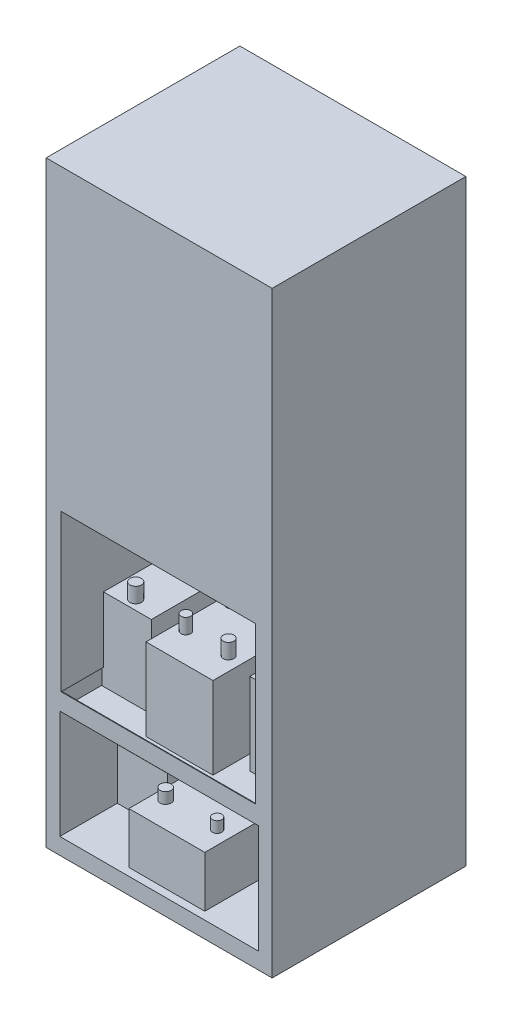
SolidWorks part; units mm, degrees
ref_plane "Alzado" through (0, 0, 0) normal (0, 0, 1) x (1, 0, 0)
ref_plane "Planta" through (0, 0, 0) normal (0, 1, 0) x (1, 0, 0)
ref_plane "Vista lateral" through (0, 0, 0) normal (1, 0, 0) x (0, 0, -1)
sketch "Croquis1" plane through (0, 0, 0) normal (0, 1, 0) x (1, 0, 0)
  line L1 (-350, 300) -> (350, 300)
  line L2 (-350, 300) -> (-350, -300)
  line L3 (-350, -300) -> (350, -300)
  line L4 (350, 300) -> (350, -300)
  line L5 (-350, 300) -> (350, -300) construction
  line L6 (-350, -300) -> (350, 300) construction
  point P0 (0, 0)
  dimension "D1" = 700
  dimension "D2" = 600
extrude "Saliente-Extruir1" add sketch "Croquis1" along normal blind 1850
sketch "Croquis2" plane through (0, 0, 300) normal (0, 0, 1) x (1, 0, 0)
  line L1 (-307.6068, 50.9) -> (307.6068, 50.9)
  line L2 (-307.6068, 50.9) -> (-307.6068, 387.2896)
  line L3 (-307.6068, 387.2896) -> (307.6068, 387.2896)
  line L4 (307.6068, 50.9) -> (307.6068, 387.2896)
  line L5 (-307.6068, 50.9) -> (307.6068, 387.2896) construction
  line L6 (-307.6068, 387.2896) -> (307.6068, 50.9) construction
  point P0 (0, 219.0948)
  point P5 (0, 219.0948)
extrude "Cortar-Extruir1" cut sketch "Croquis2" against normal blind 1850
sketch "Croquis3" plane through (0, 0, 300) normal (0, 0, 1) x (1, 0, 0)
  line L1 (-303.7405, 925) -> (297.7312, 925)
  line L2 (-303.7405, 925) -> (-303.7405, 440.9417)
  line L3 (-303.7405, 440.9417) -> (297.7312, 440.9417)
  line L4 (297.7312, 925) -> (297.7312, 440.9417)
  line L5 (-303.7405, 925) -> (297.7312, 440.9417) construction
  line L6 (-303.7405, 440.9417) -> (297.7312, 925) construction
  point P0 (-3.0046, 682.9709)
  point P5 (297.7312, 929.4263)
  point P6 (-303.7405, 925)
extrude "Cortar-Extruir2" cut sketch "Croquis3" against normal blind 1850
shell "Vaciado1" thickness 2 removed face at (-3.0046, 440.9417, 0)
sketch "Croquis4" plane through (0, 389.2896, 0) normal (0, 1, 0) x (1, 0, 0)
  line L1 (149.6111, 168.6997) -> (305.4222, 168.6997)
  line L2 (149.6111, 168.6997) -> (149.6111, -168.6997)
  line L3 (149.6111, -168.6997) -> (305.4222, -168.6997)
  line L4 (305.4222, 168.6997) -> (305.4222, -168.6997)
  line L5 (149.6111, 168.6997) -> (305.4222, -168.6997) construction
  line L6 (149.6111, -168.6997) -> (305.4222, 168.6997) construction
  line L7 (-103.6465, 236.9965) -> (103.6465, 236.9965)
  line L8 (-103.6465, 236.9965) -> (-103.6465, -236.9965)
  line L9 (-103.6465, -236.9965) -> (103.6465, -236.9965)
  line L10 (103.6465, 236.9965) -> (103.6465, -236.9965)
  line L11 (-103.6465, 236.9965) -> (103.6465, -236.9965) construction
  line L12 (-103.6465, -236.9965) -> (103.6465, 236.9965) construction
  line L13 (-308.6569, 166.2136) -> (-155.4697, 166.2136)
  line L14 (-308.6569, 166.2136) -> (-308.6569, -168.6997)
  line L15 (-308.6569, -168.6997) -> (-155.4697, -168.6997)
  line L16 (-155.4697, 166.2136) -> (-155.4697, -168.6997)
  line L17 (-308.6569, 166.2136) -> (-155.4697, -168.6997) construction
  line L18 (-308.6569, -168.6997) -> (-155.4697, 166.2136) construction
  point P0 (227.5167, 0)
  point P5 (0, 0)
  point P11 (-232.0633, -1.2431)
  point P16 (227.5167, 0)
  point P17 (-206.029, 0)
  point P18 (103.6465, 236.9965)
  point P19 (-236.3645, 0)
  point P20 (-155.4697, 166.2136)
extrude "Saliente-Extruir2" add sketch "Croquis4" along normal blind 254
sketch "Croquis5" plane through (0, 643.2896, 0) normal (0, 1, 0) x (1, 0, 0)
  circle A0 centre (230.0446, -120.7102) radius 17.6957
  circle A1 centre (230.0446, 47.3993) radius 17.6957
  circle A2 centre (-71.1508, -146.027) radius 14.8785
  circle A3 centre (-71.1508, 0) radius 20.0461
  circle A4 centre (-234.15, -138.406) radius 17.6957
  circle A5 centre (-234.15, 47.3993) radius 15.6127
  circle A6 centre (-71.1508, 166.6036) radius 20.0697
  circle A7 centre (61.0037, 0) radius 21.5153
  circle A8 centre (61.0037, 166.6036) radius 19.1168
  circle A9 centre (61.0037, -146.027) radius 16.4298
extrude "Saliente-Extruir3" add sketch "Croquis5" along normal blind 47
sketch "Croquis6" plane through (0, 50.9, 0) normal (0, 1, 0) x (1, 0, 0)
  line L1 (117.5503, -276.1799) -> (-117.5503, -276.1799)
  line L2 (117.5503, -276.1799) -> (117.5503, 276.1799)
  line L3 (117.5503, 276.1799) -> (-117.5503, 276.1799)
  line L4 (-117.5503, -276.1799) -> (-117.5503, 276.1799)
  line L5 (117.5503, -276.1799) -> (-117.5503, 276.1799) construction
  line L6 (117.5503, 276.1799) -> (-117.5503, -276.1799) construction
  line L7 (-152.4825, -121.9742) -> (-307.6068, -121.9742)
  line L8 (-152.4825, -121.9742) -> (-152.4825, 121.9742)
  line L9 (-152.4825, 121.9742) -> (-307.6068, 121.9742)
  line L10 (-307.6068, -121.9742) -> (-307.6068, 121.9742)
  line L11 (-152.4825, -121.9742) -> (-307.6068, 121.9742) construction
  line L12 (-152.4825, 121.9742) -> (-307.6068, -121.9742) construction
  line L13 (289.4517, -121.9742) -> (152.9417, -121.9742)
  line L14 (289.4517, -121.9742) -> (289.4517, 121.9742)
  line L15 (289.4517, 121.9742) -> (152.9417, 121.9742)
  line L16 (152.9417, -121.9742) -> (152.9417, 121.9742)
  line L17 (289.4517, -121.9742) -> (152.9417, 121.9742) construction
  line L18 (289.4517, 121.9742) -> (152.9417, -121.9742) construction
  point P0 (0, 0)
  point P6 (-230.0446, 0)
  point P11 (221.1967, 0)
  point P16 (117.5503, 276.1799)
extrude "Saliente-Extruir4" add sketch "Croquis6" along normal blind 158
sketch "Croquis7" plane through (0, 208.9, 0) normal (0, 1, 0) x (1, 0, 0)
  circle A0 centre (220.4901, -83.4417) radius 21.3099
  circle A1 centre (220.4901, 65.5487) radius 19.7092
  circle A2 centre (-83.7177, -196.0122) radius 17.1385
  circle A3 centre (75.6701, -196.0122) radius 14.5387
  circle A4 centre (-83.7177, 0) radius 19.1962
  circle A5 centre (75.6701, 5.9526) radius 15.4246
  circle A6 centre (-83.7177, 184.741) radius 17.9954
  circle A7 centre (75.6701, 184.741) radius 20.52
  circle A8 centre (-230.0446, -62.1317) radius 17.445
  circle A9 centre (-230.0446, 45.8395) radius 21.1159
extrude "Saliente-Extruir5" add sketch "Croquis7" along normal blind 34
sketch "Croquis8" plane through (0, 0, -300) normal (0, 0, -1) x (-1, 0, 0)
  line L1 (-250.0903, 1244.3934) -> (250.0903, 1244.3934)
  line L2 (-300.0903, 1294.3934) -> (-300.0903, 1716.6284)
  line L3 (-250.0903, 1766.6284) -> (250.0903, 1766.6284)
  line L4 (300.0903, 1294.3934) -> (300.0903, 1716.6284)
  line L5 (-300.0903, 1244.3934) -> (300.0903, 1766.6284) construction
  line L6 (-300.0903, 1766.6284) -> (300.0903, 1244.3934) construction
  arc A0 (-250.0903, 1244.3934) -> (-300.0903, 1294.3934) centre (-250.0903, 1294.3934) cw
  arc A1 (250.0903, 1244.3934) -> (300.0903, 1294.3934) centre (250.0903, 1294.3934) ccw
  arc A2 (250.0903, 1766.6284) -> (300.0903, 1716.6284) centre (250.0903, 1716.6284) cw
  arc A3 (-300.0903, 1716.6284) -> (-250.0903, 1766.6284) centre (-250.0903, 1716.6284) cw
  point P0 (0, 1505.5109)
  point P5 (0, 1570.6251)
  point P6 (0, 1505.5109)
  dimension "D1" = 50
extrude "Saliente-Extruir6" add sketch "Croquis8" along normal blind 34
sketch "Croquis9" plane through (0, 0, -334) normal (0, 0, -1) x (-1, 0, 0)
  line L1 (-278.6006, 1733.8635) -> (-181.3334, 1733.8635)
  line L2 (-278.6006, 1733.8635) -> (-278.6006, 1654.2812)
  line L3 (-278.6006, 1654.2812) -> (-181.3334, 1654.2812)
  line L4 (-181.3334, 1733.8635) -> (-181.3334, 1654.2812)
  line L5 (-278.6006, 1733.8635) -> (-181.3334, 1654.2812) construction
  line L6 (-278.6006, 1654.2812) -> (-181.3334, 1733.8635) construction
  line L7 (-2.0629, 1491.6936) -> (254.3691, 1491.6936)
  line L8 (-2.0629, 1491.6936) -> (-2.0629, 1336.9502)
  line L9 (-2.0629, 1336.9502) -> (254.3691, 1336.9502)
  line L10 (254.3691, 1491.6936) -> (254.3691, 1336.9502)
  line L11 (-2.0629, 1491.6936) -> (254.3691, 1336.9502) construction
  line L12 (-2.0629, 1336.9502) -> (254.3691, 1491.6936) construction
  point P0 (-229.967, 1694.0724)
  point P5 (126.1531, 1414.3219)
  point P10 (126.1531, 1414.3219)
extrude "Cortar-Extruir3" cut sketch "Croquis9" against normal blind 0.2
sketch "Croquis10" plane through (0, 0, -334) normal (0, 0, -1) x (-1, 0, 0)
  line L0 (-266.9064, 1336.5019) -> (-114.6168, 1336.5019) construction
  text T0 "MEJ" font "Century Gothic" height in points 250
extrude "Cortar-Extruir4" cut sketch "Croquis10" against normal blind 0.2
sketch "Croquis11" plane through (0, 0, -300) normal (0, 0, -1) x (-1, 0, 0)
  circle A0 centre (-331.1303, 1826.0494) radius 8.6382
  circle A1 centre (331.4196, 1826.0494) radius 9.502
extrude "Cortar-Extruir5" cut sketch "Croquis11" against normal blind 0.2
pattern_linear "MatrizL1" count 36 spacing 50 along (0, -1, 0) of "Cortar-Extruir5"
sketch "Croquis12" plane through (0, 0, -300) normal (0, 0, -1) x (-1, 0, 0)
  circle A0 centre (-277.5665, 414.7202) radius 7.9
extrude "Cortar-Extruir6" cut sketch "Croquis12" against normal blind 0.2
pattern_linear "MatrizL2" count 30 spacing 20 along (-1, 0, 0) of "Cortar-Extruir6"
